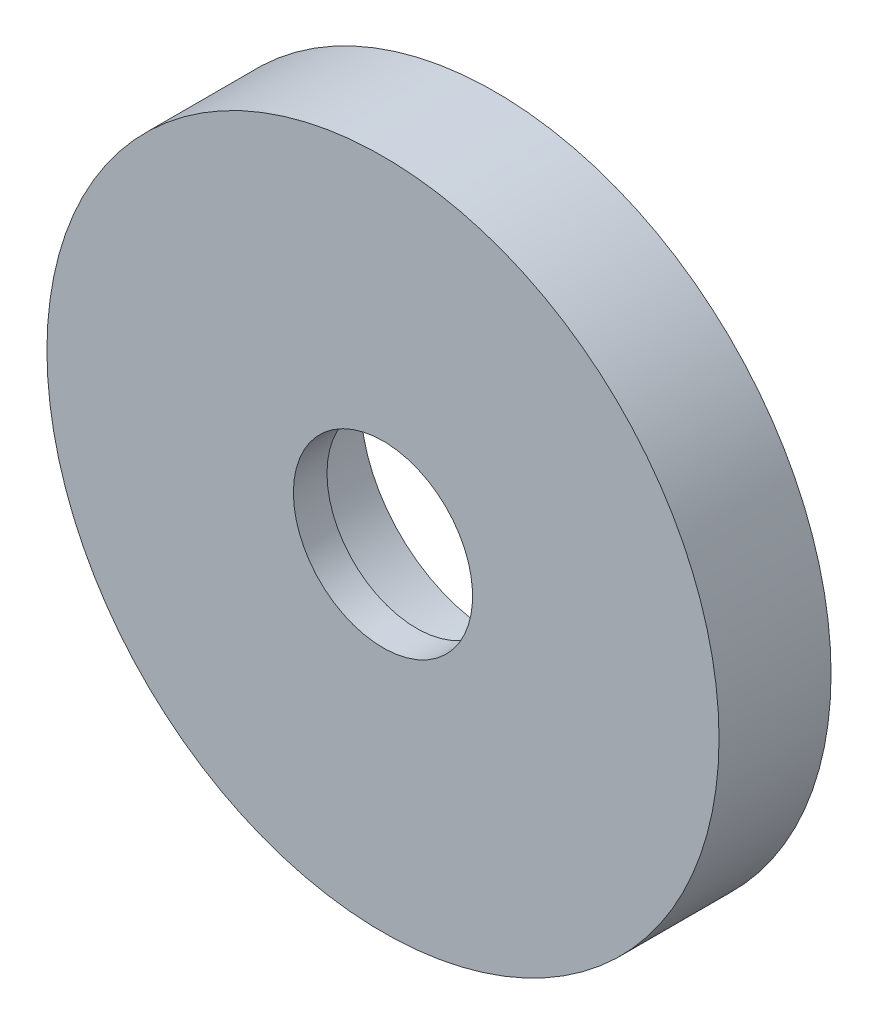
SolidWorks part; units mm, degrees
ref_plane "Front Plane" through (0, 0, 0) normal (0, 0, 1) x (1, 0, 0)
ref_plane "Top Plane" through (0, 0, 0) normal (0, 1, 0) x (1, 0, 0)
ref_plane "Right Plane" through (0, 0, 0) normal (1, 0, 0) x (0, 0, -1)
sketch "Sketch1" plane through (0, 0, 0) normal (0, 0, 1) x (1, 0, 0)
  line L8 (-5, 9.45) -> (5, 9.45)
  line L9 (5.625, 10.075) -> (5.625, 11.8645)
  line L10 (2.7632, 13.2) -> (-2.7632, 13.2)
  line L11 (-5.625, 11.8645) -> (-5.625, 10.075)
  line L12 (-5, 9.45) -> (5, 9.45)
  line L13 (5.625, 10.075) -> (5.625, 11.8645)
  line L14 (2.7632, 13.2) -> (-2.7632, 13.2)
  line L15 (-5.625, 11.8645) -> (-5.625, 10.075)
  circle A8 centre (0, 0) radius 15
  arc A16 (5, 9.45) -> (5.625, 10.075) centre (5, 10.075) ccw
  arc A17 (5.625, 11.8645) -> (5.2427, 12.4404) centre (5, 11.8645) ccw
  arc A18 (5.2427, 12.4404) -> (2.8973, 13.1854) centre (0, 0) ccw
  arc A19 (2.8973, 13.1854) -> (2.7632, 13.2) centre (2.7632, 12.575) ccw
  arc A20 (-2.7632, 13.2) -> (-2.8973, 13.1854) centre (-2.7632, 12.575) ccw
  arc A21 (-2.8973, 13.1854) -> (-5.2427, 12.4404) centre (0, 0) ccw
  arc A22 (-5.2427, 12.4404) -> (-5.625, 11.8645) centre (-5, 11.8645) ccw
  arc A23 (-5.625, 10.075) -> (-5, 9.45) centre (-5, 10.075) ccw
  arc A24 (5, 9.45) -> (5.625, 10.075) centre (5, 10.075) ccw
  arc A25 (5.625, 11.8645) -> (5.2427, 12.4404) centre (5, 11.8645) ccw
  arc A26 (5.2427, 12.4404) -> (2.8973, 13.1854) centre (0, 0) ccw
  arc A27 (2.8973, 13.1854) -> (2.7632, 13.2) centre (2.7632, 12.575) ccw
  arc A28 (-2.7632, 13.2) -> (-2.8973, 13.1854) centre (-2.7632, 12.575) ccw
  arc A29 (-2.8973, 13.1854) -> (-5.2427, 12.4404) centre (0, 0) ccw
  arc A30 (-5.2427, 12.4404) -> (-5.625, 11.8645) centre (-5, 11.8645) ccw
  arc A31 (-5.625, 10.075) -> (-5, 9.45) centre (-5, 10.075) ccw
  dimension "D2" = 30
  dimension "D1" = 0.625
extrude "Boss-Extrude1" add sketch "Sketch1" along normal blind 5 contours A8
extrude "Cut-Extrude1" cut sketch "Sketch1<3>" along normal blind 2.75 contours L15 A31 L12 A24 L13 A25 A26 A27 L14 A28 A29 A30 region at (0, 11.2402, 0)
sketch "Sketch1<3>" plane through (0, 0, 0) normal (0, 0, 1) x (1, 0, 0) same geometry as "Sketch1"
ref_axis "Axis1" through (0, 0, 5.25) along (0, 0, -1)
pattern_circular "CirPattern1" count 4 over 360 about axis through (0, 0, 5.25) along (0, 0, -1) of "Cut-Extrude1"
sketch "Sketch2" plane through (0, 0, 0) normal (0, 0, -1) x (-1, 0, 0)
  circle A0 centre (0, 0) radius 4
  circle A1 centre (0, 0) radius 6
  dimension "D1" = 8
  dimension "D2" = 12
extrude "Cut-Extrude2" cut sketch "Sketch2" against normal through all contours A0 region at (0, 0, 0)
extrude "Cut-Extrude3" cut sketch "Sketch2<3>" against normal blind 3.5
sketch "Sketch2<3>" plane through (0, 0, 0) normal (0, 0, -1) x (-1, 0, 0) same geometry as "Sketch2"
